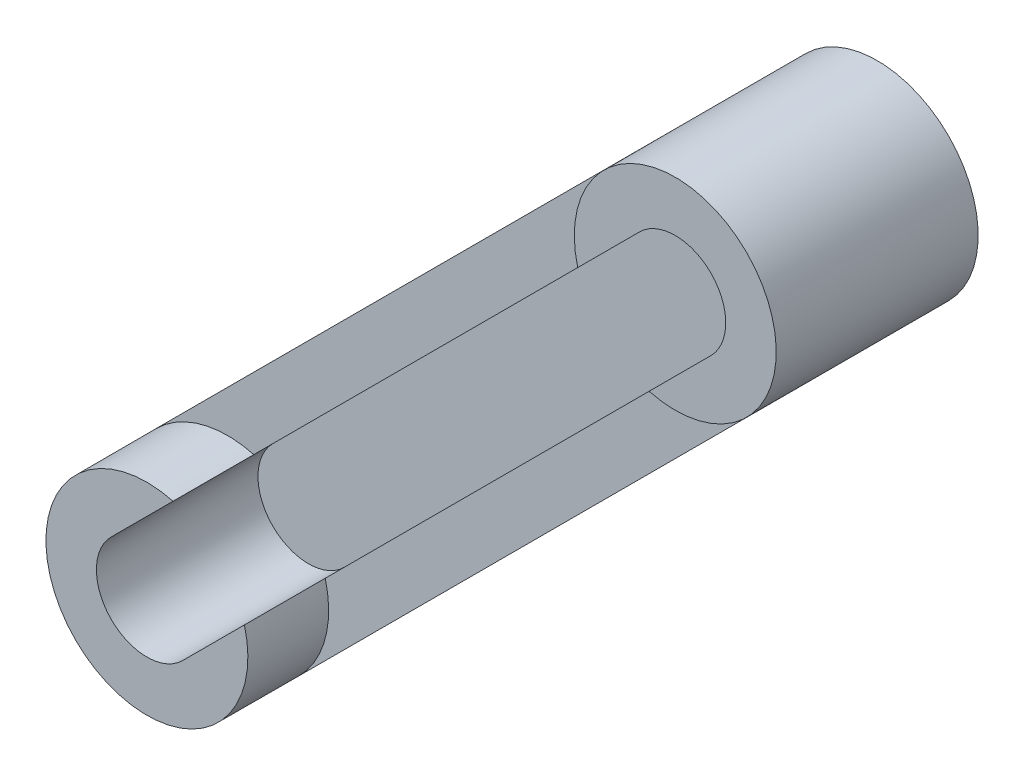
SolidWorks part; units mm, degrees
ref_plane "Спереди" through (0, 0, 0) normal (0, 0, 1) x (1, 0, 0)
ref_plane "Сверху" through (0, 0, 0) normal (0, 1, 0) x (1, 0, 0)
ref_plane "Справа" through (0, 0, 0) normal (1, 0, 0) x (0, 0, -1)
sketch "Эскиз1" plane through (0, 0, 0) normal (0, 0, 1) x (1, 0, 0)
  line L0 (-73.4107, 0) -> (65.3283, 0) construction
  line L1 (-11.2779, 1.2019) -> (-37.4408, -24.961) construction
  circle A0 centre (-11.2779, 1.2019) radius 2.5
  circle A1 centre (-11.2779, 1.2019) radius 5
  circle A2 centre (-37.4408, -24.961) radius 2.5
  circle A3 centre (-37.4408, -24.961) radius 5
  dimension "D2" = 5
  dimension "D3" = 10
  dimension "D1" = 45
  dimension "D4" = 37
  dimension "D8" = 11.2779
  dimension "D9" = 1.2019
extrude "Бобышка-Вытянуть1" add sketch "Эскиз1" along normal blind 10
sketch "Эскиз3" plane through (0, 0, 0) normal (0, 0, -1) x (-1, 0, 0)
  line L0 (11.2779, 1.2019) -> (14.8134, 4.7375)
  line L1 (14.8134, 4.7375) -> (40.9763, -21.4255)
  line L2 (40.9763, -21.4255) -> (33.9053, -28.4966)
  line L3 (33.9053, -28.4966) -> (7.7423, -2.3336)
  line L4 (7.7423, -2.3336) -> (11.2779, 1.2019)
  circle A0 centre (11.2779, 1.2019) radius 5 construction
  circle A1 centre (37.4408, -24.961) radius 5 construction
extrude "Бобышка-Вытянуть2" add sketch "Эскиз3" against normal blind 6
sketch "Эскиз4" plane through (0, 0, 6) normal (0, 0, 1) x (1, 0, 0)
  line L0 (-13.0456, 2.9697) -> (-9.5101, -0.5658)
  line L1 (-13.0456, 2.9697) -> (-9.5101, -0.5658) construction
  line L2 (-9.5101, -0.5658) -> (-35.673, -26.7288)
  line L3 (-35.673, -26.7288) -> (-39.2086, -23.1933) construction
  line L4 (-35.673, -26.7288) -> (-39.2086, -23.1933)
  line L5 (-39.2086, -23.1933) -> (-13.0456, 2.9697)
  line L6 (-7.7423, -2.3336) -> (-33.9053, -28.4966) construction
  line L8 (-40.9763, -21.4255) -> (-14.8134, 4.7375) construction
  dimension "D1" = 2.5
  dimension "D2" = 2.5
extrude "Вырез-Вытянуть1" cut sketch "Эскиз4" against normal blind 4
sketch "Эскиз5" plane through (0, 0, 0) normal (0, 0, -1) x (-1, 0, 0)
  line L0 (13.0456, 2.9697) -> (9.5101, -0.5658) construction
  line L1 (35.673, -26.7288) -> (39.2086, -23.1933) construction
  circle A0 centre (11.2779, 1.2019) radius 2.5
  circle A1 centre (37.4408, -24.961) radius 2.5
  arc A2 (35.673, -26.7288) -> (39.2086, -23.1933) centre (37.4408, -24.961) ccw construction
  arc A3 (13.0456, 2.9697) -> (9.5101, -0.5658) centre (11.2779, 1.2019) ccw construction
extrude "Бобышка-Вытянуть3" add sketch "Эскиз5" against normal blind 2
extrude "Вырез-Вытянуть2" cut sketch "Эскиз4<2>" along normal blind 4
sketch "Эскиз4<2>" plane through (0, 0, 6) normal (0, 0, 1) x (1, 0, 0) same geometry as "Эскиз4"
